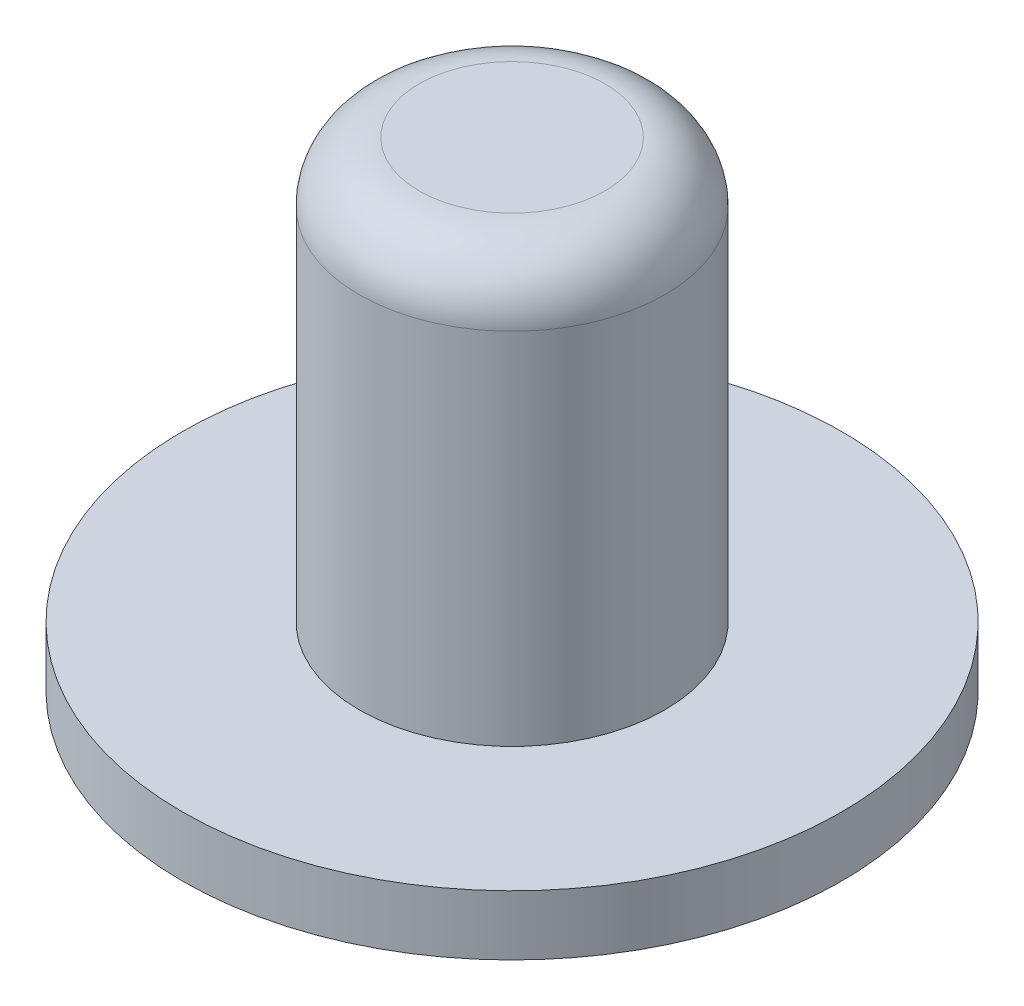
SolidWorks part; units mm, degrees
ref_plane "Front Plane" through (0, 0, 0) normal (0, 0, 1) x (1, 0, 0)
ref_plane "Top Plane" through (0, 0, 0) normal (0, 1, 0) x (1, 0, 0)
ref_plane "Right Plane" through (0, 0, 0) normal (1, 0, 0) x (0, 0, -1)
sketch "Sketch1" plane through (0, 0, 0) normal (0, 1, 0) x (1, 0, 0)
  circle A0 centre (0, 0) radius 2.55
  circle A1 centre (0, 0) radius 5.5
  dimension "D1" = 5.1
  dimension "D2" = 11
extrude "Boss-Extrude1" add sketch "Sketch1" along normal blind 7 contours A0 region at (0, 0, 0)
extrude "Boss-Extrude2" add sketch "Sketch1<3>" against normal blind 1 contours A1 A0 | A0 region at (0, 0, 0) region at (-5.3444, 0, 0)
sketch "Sketch1<3>" plane through (0, 0, 0) normal (0, 1, 0) x (1, 0, 0) same geometry as "Sketch1"
fillet "Fillet1" radius 1 1 edges at (0, 7, 2.55)
